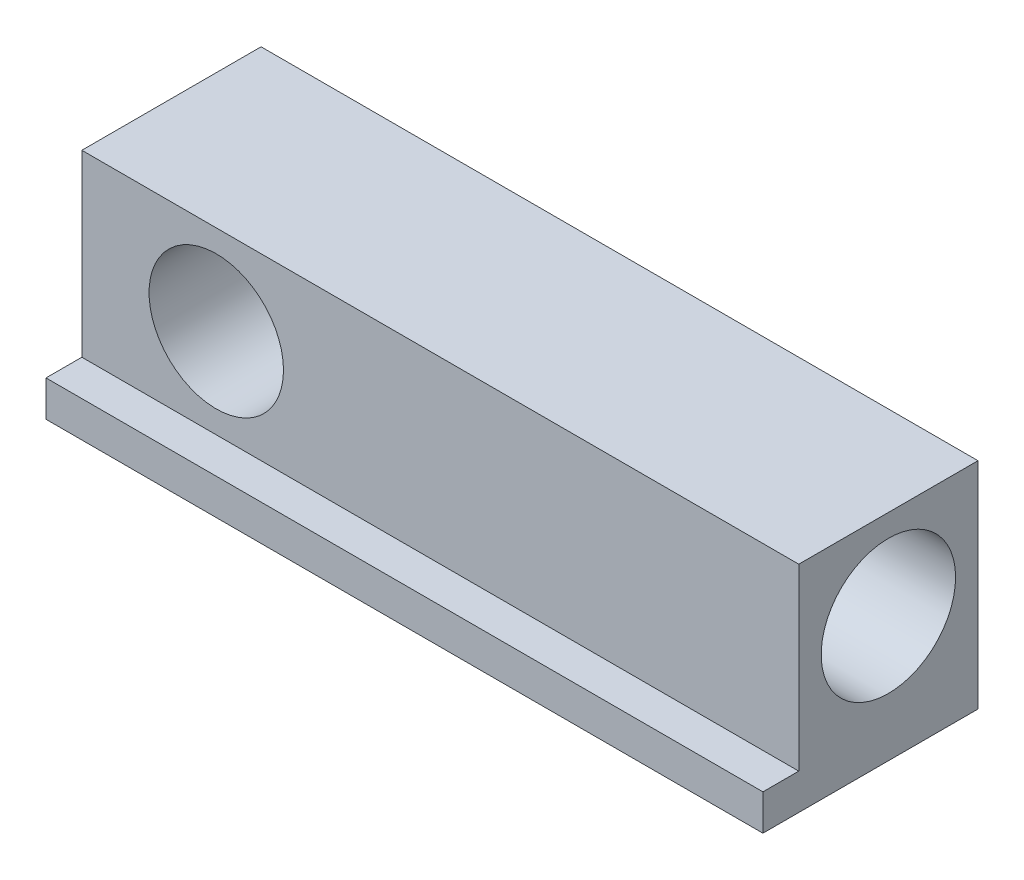
SolidWorks part; units mm, degrees
material "1060 Alloy"
ref_plane "Front Plane" through (0, 0, 0) normal (0, 0, 1) x (1, 0, 0)
ref_plane "Top Plane" through (0, 0, 0) normal (0, 1, 0) x (1, 0, 0)
ref_plane "Right Plane" through (0, 0, 0) normal (1, 0, 0) x (0, 0, -1)
sketch "Sketch1" plane through (0, 0, 0) normal (1, 0, 0) x (0, 0, -1)
  line L1 (-10, -10) -> (10, -10)
  line L2 (-10, -10) -> (-10, 10)
  line L3 (-10, 10) -> (10, 10)
  line L4 (10, -10) -> (10, 10)
  line L5 (-10, -10) -> (10, 10) construction
  line L6 (-10, 10) -> (10, -10) construction
  point P0 (0, 0)
  dimension "D1" = 20
  dimension "D2" = 20
extrude "Boss-Extrude1" add sketch "Sketch1" along normal mid plane 80
sketch "Sketch4" plane through (0, 0, 0) normal (0, 0, 1) x (1, 0, 0)
  line L0 (40, -10) -> (-40, -10) construction
  line L1 (-40, 10) -> (-40, -10) construction
  circle A0 centre (-25, 0) radius 7.5
  dimension "D2" = 15
  dimension "D1" = 10
  dimension "D3" = 15
extrude "Cut-Extrude1" cut sketch "Sketch4" against normal through all both and the other way through all
sketch "Sketch11" plane through (0, -10, 0) normal (0, -1, 0) x (1, 0, 0)
  line L0 (40, 10) -> (40, -10) construction
  line L1 (-40, 10) -> (40, 10)
  line L2 (-40, 10) -> (-40, -14)
  line L3 (-40, -14) -> (40, -14)
  line L4 (40, 10) -> (40, -14)
  dimension "D1" = 24
extrude "Boss-Extrude2" [suppressed] add sketch "Sketch11" along normal blind 4
sketch "Sketch12" plane through (40, 0, 0) normal (1, 0, 0) x (0, 0, -1)
  circle A0 centre (0, 0) radius 7.5
  dimension "D1" = 15
extrude "Cut-Extrude3" cut sketch "Sketch12" against normal blind 40
sketch "Sketch13" plane through (0, -10, 0) normal (0, -1, 0) x (1, 0, 0)
  line L0 (-40, 10) -> (-40, -10) construction
  line L1 (40, -10) -> (-40, -10)
  line L2 (40, -10) -> (40, 14)
  line L3 (40, 14) -> (-40, 14)
  line L4 (-40, -10) -> (-40, 14)
  dimension "D1" = 24
extrude "Boss-Extrude3" add sketch "Sketch13" along normal blind 4
move or copy body "Body-Move/Copy1" [suppressed] bodies to move or copy 108
move or copy body "Body-Move/Copy2" [suppressed] bodies to move or copy 107
